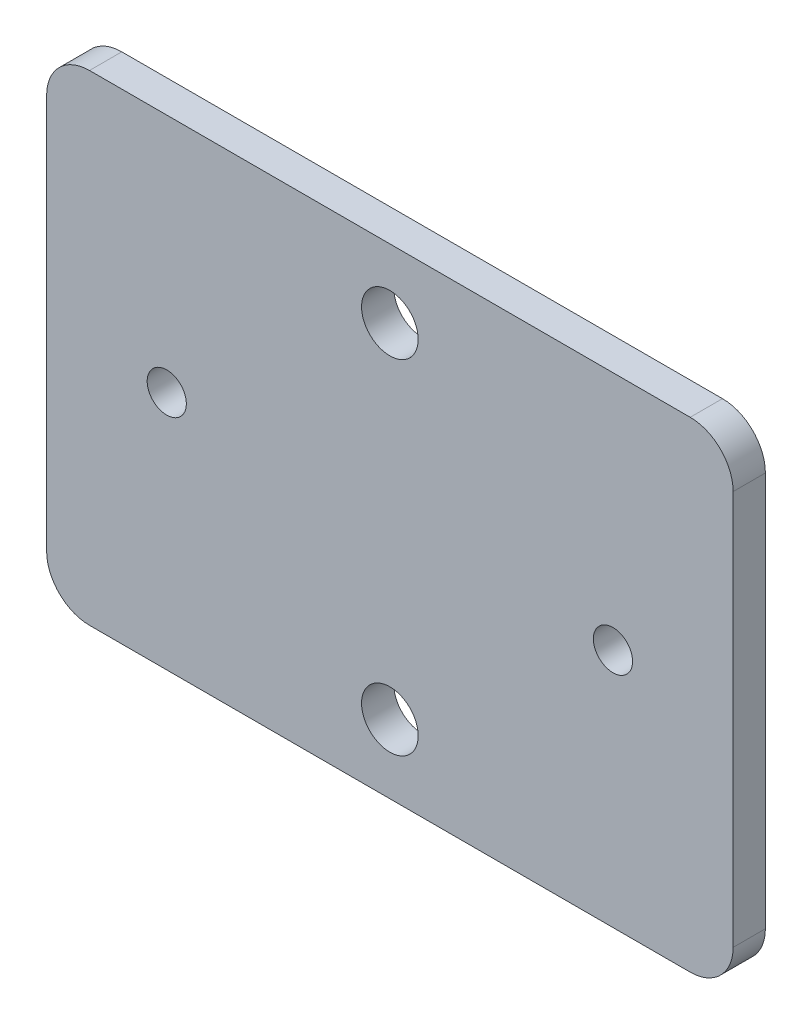
SolidWorks part; units mm, degrees
ref_plane "Front Plane" through (0, 0, 0) normal (0, 0, 1) x (1, 0, 0)
ref_plane "Top Plane" through (0, 0, 0) normal (0, 1, 0) x (1, 0, 0)
ref_plane "Right Plane" through (0, 0, 0) normal (1, 0, 0) x (0, 0, -1)
sketch "Sketch1" plane through (0, 0, 0) normal (0, 0, 1) x (1, 0, 0)
  line L0 (-50.8, -50.8) -> (50.8, -50.8) construction
  line L1 (-50.8, 50.8) -> (-50.8, -50.8) construction
  line L2 (50.8, -50.8) -> (50.8, -25.4) construction
  line L3 (-38.1, -34.8361) -> (-38.1, -41.3639) construction
  point P3 (0, -50.8)
  point P8 (-50.8, 0)
  point P9 (-38.1, -38.1)
  point P10 (50.8, -38.1)
  point P11 (0, 50.8)
  point P12 (-12.7, -38.1)
sketch "Sketch2" plane through (0, 0, 0) normal (1, 0, 0) x (0, 0, -1)
  line L0 (2.3876, 0) -> (-2.3876, 0) construction
  point P4 (0, 0)
  dimension "Thickness" = 4.7752
sketch "Sketch3" plane through (0, 0, 0) normal (0, 0, 1) x (1, 0, 0)
  line L0 (50.8, -25.4) -> (50.8, -50.8)
  line L1 (50.8, -50.8) -> (-50.8, -50.8)
  line L2 (-50.8, -50.8) -> (-50.8, 50.8)
  line L3 (-50.8, 50.8) -> (-25.4, 50.8)
  line L4 (-25.4, 50.8) -> (50.8, -25.4)
extrude "Boss-Extrude1" add sketch "Sketch3" against normal up to vertex (2.3876 mm away) and the other way up to vertex (2.3876 mm away) up to point (0, 0, -2.3876) other way up to point (0, 0, 2.3876)
sketch "Sketch4" plane through (0, 0, 2.3876) normal (0, 0, 1) x (1, 0, 0)
  line L0 (-38.1, -34.8361) -> (-38.1, -41.3639) construction
  line L1 (-50.8, -50.8) -> (0, 0) construction
  line L2 (-38.1, -38.1) -> (-12.7, -38.1) construction
  line L3 (-38.1, -38.1) -> (-38.1, -12.7) construction
  circle A0 centre (-38.1, -38.1) radius 3.2639
  circle A5 centre (-12.7, -38.1) radius 3.2639
  circle A6 centre (12.7, -38.1) radius 3.2639
  circle A7 centre (-38.1, -12.7) radius 3.2639
  circle A8 centre (-38.1, 12.7) radius 3.2639
  circle A9 centre (38.1, -38.1) radius 3.2639
  circle A10 centre (-38.1, 38.1) radius 3.2639
  dimension "D2" = 25.4
  dimension "D4" = 25.4
  dimension "D1" = 4
  dimension "D3" = 4
extrude "Cut-Extrude1" cut sketch "Sketch4" against normal through all
sketch "Sketch7" plane through (0, 0, 2.3876) normal (0, 0, 1) x (1, 0, 0)
  line L0 (50.8, -50.8) -> (50.8, -25.4) construction
  line L1 (-50.8, -50.8) -> (50.8, -50.8)
  line L2 (-50.8, -50.8) -> (-50.8, 50.8)
  line L3 (-50.8, 50.8) -> (50.8, 50.8)
  line L4 (50.8, -50.8) -> (50.8, 50.8)
extrude "Boss-Extrude2" add sketch "Sketch7" against normal up to surface (4.7752 mm away) up to face at (-9.4361, -38.1, -2.3876)
sketch "Sketch10" plane through (0, 0, 2.3876) normal (0, 0, 1) x (1, 0, 0)
  line L0 (0, 0) -> (-80.2914, 0) construction
  circle A0 centre (-33.02, 0) radius 2.9
  circle A1 centre (33.02, 0) radius 2.9
  circle A2 centre (0, 25.4) radius 4.191
  circle A3 centre (0, -25.4) radius 4.191
  dimension "D1" = 5.8
  dimension "D4" = 8.382
  dimension "D2" = 33.02
  dimension "D3" = 33.02
  dimension "D5" = 25.4
extrude "Cut-Extrude3" cut sketch "Sketch10" against normal through all
sketch "Sketch11" plane through (0, 0, 2.3876) normal (0, 0, 1) x (1, 0, 0)
  line L0 (50.8, -50.8) -> (50.8, 50.8) construction
  line L1 (-50.8, -35.56) -> (50.8, -35.56)
  line L2 (-50.8, -35.56) -> (-50.8, 35.56)
  line L3 (-50.8, 35.56) -> (50.8, 35.56)
  line L4 (50.8, -35.56) -> (50.8, 35.56)
  line L5 (-50.8, -35.56) -> (50.8, 35.56) construction
  line L6 (-50.8, 35.56) -> (50.8, -35.56) construction
  line L7 (50.8, 50.8) -> (-50.8, 50.8) construction
  point P0 (0, 0)
  dimension "D1" = 15.24
extrude "Cut-Extrude4" cut sketch "Sketch11" against normal up to next (4.7752 mm away) flip side to cut
fillet "Fillet1" radius 6.35 4 edges at (-50.8, 35.56, 0) (50.8, 35.56, 0) (50.8, -35.56, 0) (-50.8, -35.56, 0)
equation "\"D2@Sketch4\"=\"Hole Spacing@Sketch1\""
equation "\"D1@Sketch4\"=\"#Holes@Sketch1\""
equation "\"D4@Sketch4\"=\"Hole Spacing@Sketch1\""
equation "\"D3@Sketch4\"=\"#Holes@Sketch1\""
equation "\"D3@Sketch10\"=\"D2@Sketch10\""
